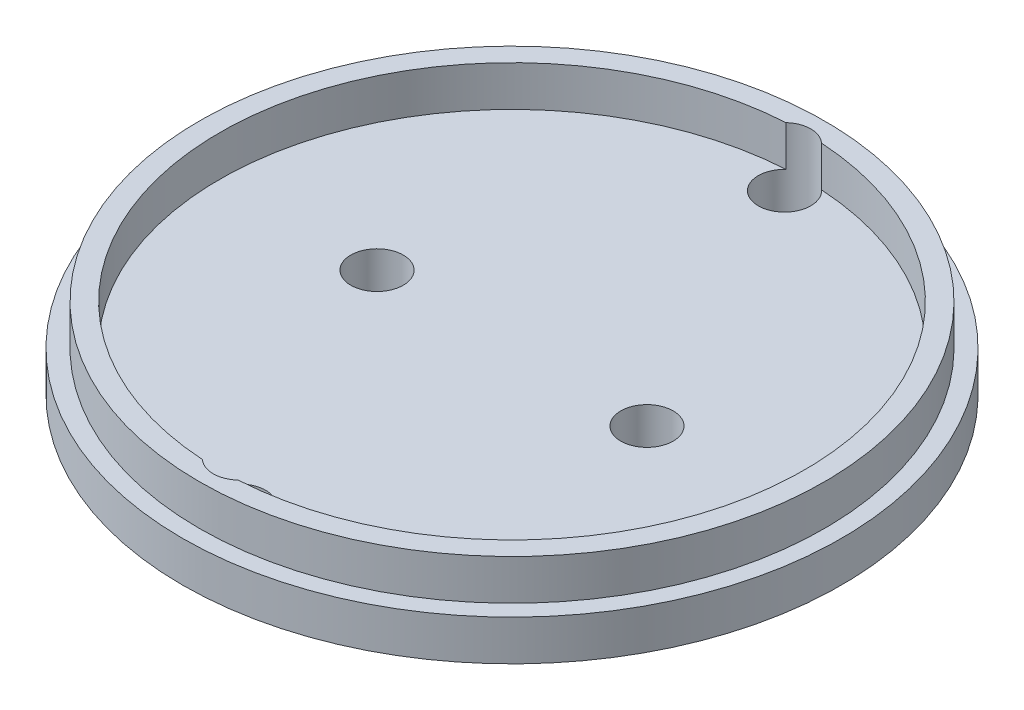
SolidWorks part; units mm, degrees
ref_plane "Front Plane" through (0, 0, 0) normal (0, 0, 1) x (1, 0, 0)
ref_plane "Top Plane" through (0, 0, 0) normal (0, 1, 0) x (1, 0, 0)
ref_plane "Right Plane" through (0, 0, 0) normal (1, 0, 0) x (0, 0, -1)
sketch "Sketch1" plane through (0, 0, 0) normal (0, 1, 0) x (1, 0, 0)
  circle A0 centre (0, 0) radius 40.7
  circle A1 centre (0, 0) radius 38.6
  circle A2 centre (0, 0) radius 36.1
  dimension "D1" = 81.4
  dimension "D2" = 77.2
  dimension "D3" = 2.5
extrude "Boss-Extrude1" add sketch "Sketch1" along normal blind 5 contours A1 A2 region at (-37.5082, 0, 0)
extrude "Boss-Extrude2" add sketch "Sketch1<4>" against normal blind 5 contours A1 A2 | A2 | A0 A1 region at (-39.5488, 0, 0) region at (-37.5082, 0, 0) region at (0, 0, 0)
sketch "Sketch1<4>" plane through (0, 0, 0) normal (0, 1, 0) x (1, 0, 0) same geometry as "Sketch1"
sketch "Sketch4" plane through (0, -5, 0) normal (0, -1, 0) x (1, 0, 0)
  line L0 (16.6687, 0) -> (-16.6688, 0) construction
  line L1 (0, 33.655) -> (0, -33.655) construction
  circle A0 centre (-16.6688, 0) radius 3.2385
  circle A1 centre (16.6687, 0) radius 3.2385
  circle A2 centre (0, 33.655) radius 3.2385
  circle A3 centre (0, -33.655) radius 3.2385
  point P5 (0, 0)
  point P11 (0, 0)
  dimension "D2" = 6.477
  dimension "D4" = 6.477
  dimension "D1" = 33.3375
  dimension "D3" = 67.31
extrude "Cut-Extrude1" cut sketch "Sketch4" against normal through all both and the other way through all
